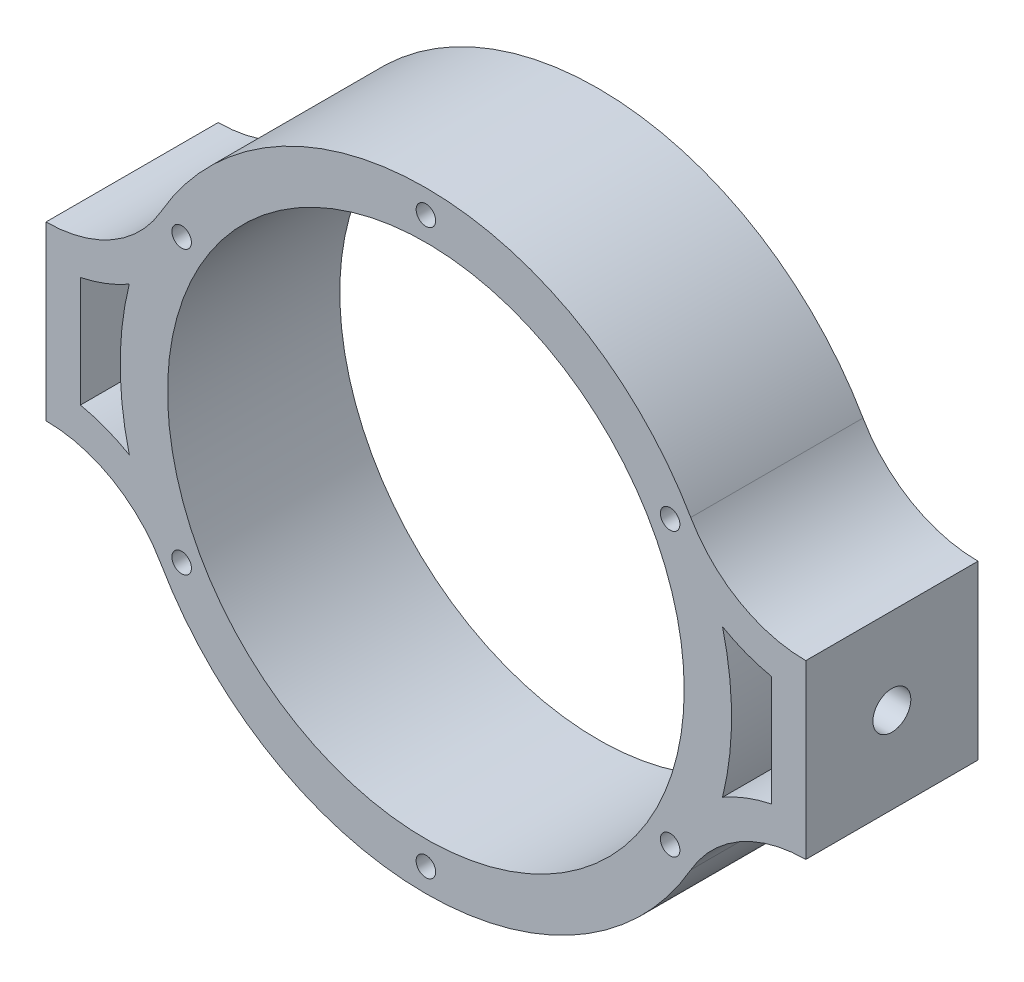
SolidWorks part; units mm, degrees
material "6061-T6 (SS)"
ref_plane "Front Plane" through (0, 0, 0) normal (0, 0, 1) x (1, 0, 0)
ref_plane "Top Plane" through (0, 0, 0) normal (0, 1, 0) x (1, 0, 0)
ref_plane "Right Plane" through (0, 0, 0) normal (1, 0, 0) x (0, 0, -1)
sketch "Sketch1" plane through (0, 0, 0) normal (0, 0, 1) x (1, 0, 0)
  line L0 (-66.175, 0) -> (66.175, 0) construction
  line L1 (-66.175, -15) -> (-66.175, 15)
  line L2 (-66.175, 15) -> (-51.0937, 15) construction
  line L3 (0, 0) -> (0, 53.25) construction
  line L4 (66.175, -15) -> (66.175, 15)
  circle A0 centre (0, 0) radius 53.25 construction
  arc A1 (-66.175, 15) -> (-46.1423, 26.5792) centre (-66.175, 38.1185) ccw
  arc A4 (66.175, 15) -> (46.1423, 26.5792) centre (66.175, 38.1185) cw
  arc A5 (-46.1423, 26.5792) -> (46.1423, 26.5792) centre (0, 0) cw
  circle A7 centre (0, 0) radius 45
  arc A11 (66.175, -15) -> (46.1423, -26.5792) centre (66.175, -38.1185) ccw
  arc A12 (-46.1423, -26.5792) -> (46.1423, -26.5792) centre (0, 0) ccw
  arc A13 (-66.175, -15) -> (-46.1423, -26.5792) centre (-66.175, -38.1185) cw
  point P5 (0, 0)
  point P8 (-66.175, 0)
  dimension "D1" = 53.25
  dimension "D2" = 132.35
  dimension "D3" = 90
  dimension "D4" = 30
extrude "Boss-Extrude1" add sketch "Sketch1" along normal mid plane 30
sketch "Sketch2" plane through (0, 0, 15) normal (0, 0, 1) x (1, 0, 0)
  line L2 (0, 0) -> (0, -53.25) construction
  line L3 (-60.175, -9.6249) -> (-60.175, 9.6249)
  line L4 (-60.175, -9.6249) -> (-60.175, 9.6249)
  line L5 (60.175, -9.6249) -> (60.175, 9.6249)
  arc A0 (46.1423, 26.5792) -> (-46.1423, 26.5792) centre (0, 0) ccw construction
  arc A1 (46.1423, 26.5792) -> (-46.1423, 26.5792) centre (0, 0) ccw construction
  circle A2 centre (0, 0) radius 53.25 construction
  arc A7 (-51.6716, 12.869) -> (-51.6716, -12.869) centre (0, 0) ccw
  arc A8 (51.6716, 12.869) -> (51.6716, -12.869) centre (0, 0) cw
  arc A9 (-40.9432, -23.5843) -> (-60.175, -9.6249) centre (-66.175, -38.1185) ccw
  arc A10 (-60.175, 9.6249) -> (-40.9432, 23.5843) centre (-66.175, 38.1185) ccw
  arc A11 (-51.6716, -12.869) -> (-60.175, -9.6249) centre (-66.175, -38.1185) ccw
  arc A12 (-60.175, 9.6249) -> (-51.6716, 12.869) centre (-66.175, 38.1185) ccw
  arc A13 (60.175, 9.6249) -> (51.6716, 12.869) centre (66.175, 38.1185) cw
  arc A14 (51.6716, -12.869) -> (60.175, -9.6249) centre (66.175, -38.1185) cw
  dimension "D1" = 6
extrude "Cut-Extrude1" cut sketch "Sketch2" against normal through all both and the other way through all
sketch "Sketch3" plane through (-66.175, 0, 0) normal (-1, 0, 0) x (0, 0, 1)
  point P0 (0, 0)
hole_wizard "M6 Clearance Hole1" positions "Sketch3" profile "Sketch4" hole size "M6" standard "ANSI Metric"
sketch "Sketch4" plane through (-66.175, 0, 0) normal (0, 1, 0) x (0, 0, 1)
  line L0 (0, 0) -> (0, 7.9828)
  line L1 (0, 7.9828) -> (3.3, 6)
  line L2 (3.3, 6) -> (3.3, 0)
  line L5 (3.3, 0) -> (0, 0)
  line L10 (0, 7.9828) -> (-3.3, 6) construction
  line L11 (0, -6.35) -> (0, 107.95) construction
  dimension "Hole Dia." = 6.6
  dimension "Hole Depth" = 6
  dimension "Drill Angle" = 118
sketch "Sketch5" plane through (66.175, 0, 0) normal (1, 0, 0) x (0, 0, -1)
  point P0 (0, 0)
hole_wizard "M6 Clearance Hole2" positions "Sketch5" profile "Sketch6" hole size "M6" standard "ANSI Metric"
sketch "Sketch6" plane through (66.175, 0, 0) normal (0, 1, 0) x (0, 0, -1)
  line L0 (0, 0) -> (0, 7.9828)
  line L1 (0, 7.9828) -> (3.3, 6)
  line L2 (3.3, 6) -> (3.3, 0)
  line L5 (3.3, 0) -> (0, 0)
  line L10 (0, 7.9828) -> (-3.3, 6) construction
  line L11 (0, -6.35) -> (0, 107.95) construction
  dimension "Hole Dia." = 6.6
  dimension "Hole Depth" = 6
  dimension "Drill Angle" = 118
sketch "Sketch7" plane through (0, 0, 15) normal (0, 0, 1) x (1, 0, 0)
  line L0 (0, 53.25) -> (0, 45) construction
  circle A0 centre (0, 0) radius 49.125 construction
  arc A2 (46.1423, 26.5792) -> (-46.1423, 26.5792) centre (0, 0) ccw construction
  circle A3 centre (0, 0) radius 45 construction
  point P10 (0, 49.125)
  point P26 (0, 49.125)
  point P29 (0, 0)
hole_wizard "M3 Clearance Hole1" positions "Sketch7" profile "Sketch8" hole size "M3" standard "ANSI Metric" end condition through all
sketch "Sketch8" plane through (0, 49.125, 15) normal (1, 0, 0) x (0, -1, 0)
  line L0 (0, 0) -> (0, 30)
  line L1 (0, 30) -> (1.7, 30)
  line L2 (1.7, 30) -> (1.7, 0)
  line L5 (1.7, 0) -> (0, 0)
  line L11 (0, -6.35) -> (0, 107.95) construction
  dimension "Thru Hole Dia." = 3.4
  dimension "Thru Hole Depth" = 30
pattern_circular "CirPattern1" count 6 over 360 about axis through (0, 0, 15) along (0, 0, -1) of "M3 Clearance Hole1" reverse direction yes
